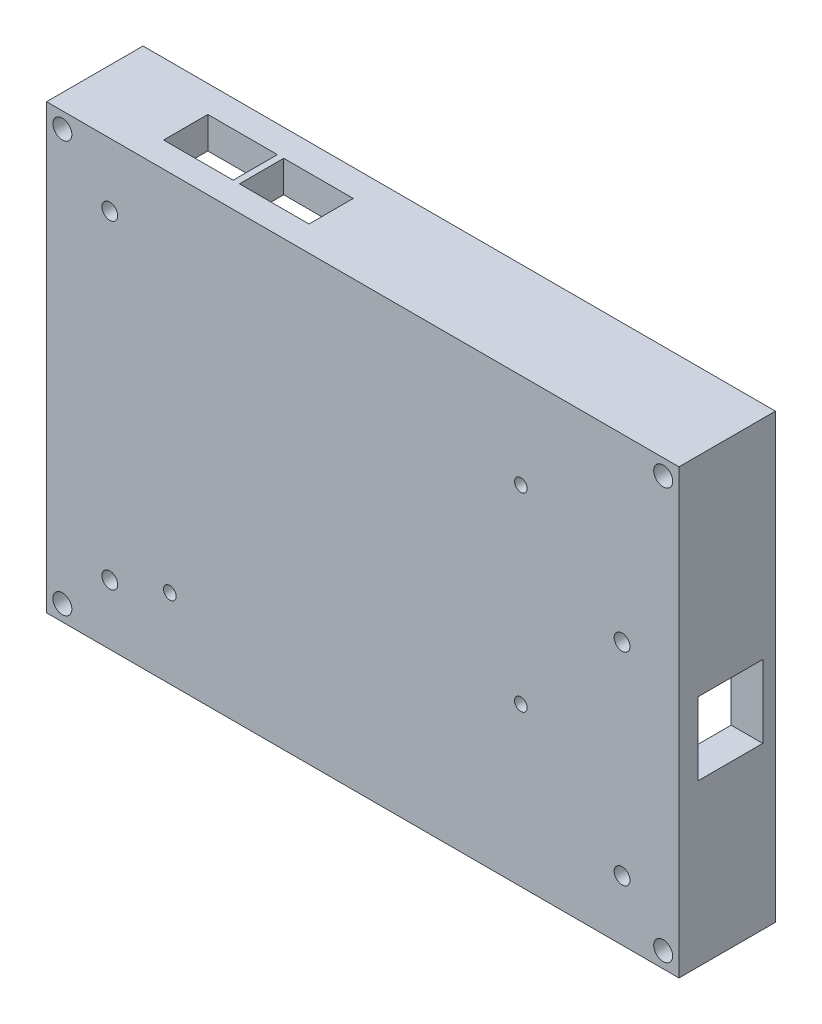
SolidWorks part; units mm, degrees
ref_plane "Front Plane" through (0, 0, 0) normal (0, 0, 1) x (1, 0, 0)
ref_plane "Top Plane" through (0, 0, 0) normal (0, 1, 0) x (1, 0, 0)
ref_plane "Right Plane" through (0, 0, 0) normal (1, 0, 0) x (0, 0, -1)
sketch "Sketch1" plane through (0, 0, 0) normal (0, 0, 1) x (1, 0, 0)
  line L0 (19.5, 57.5) -> (70.5, 57.5)
  line L1 (5, 5) -> (95, 5)
  line L2 (5, 5) -> (5, 65)
  line L3 (5, 65) -> (95, 65)
  line L4 (95, 5) -> (95, 65)
  line L5 (70.5, 57.5) -> (70.5, 27.5)
  line L6 (70.5, 27.5) -> (52.5, 27.5)
  line L7 (52.5, 27.5) -> (52.5, 12.5)
  line L8 (50, 65) -> (50, 70) construction
  line L9 (0, 0) -> (100, 0)
  line L10 (0, 0) -> (0, 70)
  line L11 (0, 70) -> (100, 70)
  line L12 (100, 0) -> (100, 70)
  line L13 (5, 35) -> (0, 35) construction
  line L14 (50, 5) -> (50, 0) construction
  line L15 (95, 35) -> (100, 35) construction
  line L16 (5, 65) -> (0, 70) construction
  line L17 (52.5, 12.5) -> (32.5, 12.5)
  line L18 (32.5, 12.5) -> (32.5, 32.5)
  line L19 (32.5, 32.5) -> (19.5, 32.5)
  line L20 (19.5, 32.5) -> (19.5, 57.5)
  line L21 (7.5, 35) -> (5, 35) construction
  line L22 (44.5, 52) -> (54.5, 52)
  line L23 (44.5, 52) -> (44.5, 46)
  line L24 (44.5, 46) -> (54.5, 46)
  line L25 (54.5, 52) -> (54.5, 46)
  line L26 (7.5, 62.5) -> (92.5, 62.5) construction
  line L27 (7.5, 62.5) -> (7.5, 7.5) construction
  line L28 (7.5, 7.5) -> (92.5, 7.5) construction
  line L29 (92.5, 62.5) -> (92.5, 7.5) construction
  line L30 (95, 35) -> (92.5, 35) construction
  line L31 (50, 5) -> (50, 7.5) construction
  line L32 (50, 65) -> (50, 62.5) construction
  line L33 (5, 12) -> (13, 12)
  line L34 (13, 12) -> (13, 5)
  line L35 (95, 13) -> (87.5, 13)
  line L36 (87.5, 13) -> (87.5, 5)
  line L37 (100, 70) -> (95, 65) construction
  line L38 (100, 0) -> (95, 5) construction
  line L39 (5, 5) -> (0, 0) construction
  line L40 (87.5, 45) -> (95, 45)
  line L41 (87.5, 45) -> (87.5, 38)
  line L42 (87.5, 38) -> (95, 38)
  line L43 (5, 56.5) -> (13.5, 56.5)
  line L44 (13.5, 56.5) -> (13.5, 65)
  line L45 (32.5, 12.5) -> (19.5, 12.5) construction
  line L46 (75, 65) -> (75, 55) construction
  line L47 (75, 55) -> (95, 55) construction
  line L48 (95, 25) -> (75, 25) construction
  line L49 (75, 25) -> (75, 5) construction
  circle A0 centre (2.5, 2.5) radius 1.5
  circle A1 centre (2.5, 67.5) radius 1.5
  circle A2 centre (97.5, 67.5) radius 1.5
  circle A3 centre (97.5, 2.5) radius 1.5
  circle A4 centre (10, 9.5) radius 0.625
  circle A5 centre (10, 60) radius 0.625
  circle A6 centre (91, 41.5) radius 0.625
  circle A7 centre (91, 9.5) radius 0.625
  circle A8 centre (10, 9.5) radius 1.25
  circle A9 centre (10, 60) radius 1.25
  circle A10 centre (91, 41.5) radius 1.25
  circle A11 centre (91, 9.5) radius 1.25
  circle A12 centre (10, 9.5) radius 1.75
  circle A13 centre (91, 9.5) radius 1.75
  circle A14 centre (91, 41.5) radius 1.75
  circle A15 centre (10, 60) radius 1.75
  circle A16 centre (19.5, 12.5) radius 1
  circle A17 centre (75, 55) radius 1
  circle A18 centre (75, 25) radius 1
  point P63 (10, 11.25)
  point P65 (11.75, 9.5)
  point P68 (91, 11.25)
  point P70 (89.25, 9.5)
  point P74 (89.25, 41.5)
  point P76 (91, 39.75)
  point P77 (91, 43.25)
  point P81 (11.75, 60)
  point P82 (10, 58.25)
  dimension "D16" = 3
  dimension "D5" = 1.25
  dimension "D14" = 2.5
  dimension "D30" = 3.5
  dimension "D31" = 0.75
  dimension "D40" = 2
  dimension "D2" = 70
  dimension "D3" = 12
  dimension "D4" = 5
  dimension "D6" = 37
  dimension "D7" = 5
  dimension "D8" = 18
  dimension "D9" = 6
  dimension "D10" = 10
  dimension "D11" = 100
  dimension "D12" = 85
  dimension "D13" = 55
  dimension "D15" = 22
  dimension "D17" = 40
  dimension "D18" = 20
  dimension "D19" = 25
  dimension "D20" = 25
  dimension "D21" = 5
  dimension "D22" = 2.5
  dimension "D23" = 2.5
  dimension "D24" = 1.5
  dimension "D25" = 21
  dimension "D26" = 1.5
  dimension "D27" = 2
  dimension "D28" = 2.5
  dimension "D29" = 2
  dimension "D32" = 1.25
  dimension "D33" = 1.75
  dimension "D34" = 1.75
  dimension "D35" = 1.75
  dimension "D36" = 1.75
  dimension "D37" = 1.75
  dimension "D38" = 1.75
  dimension "D39" = 1.75
  dimension "D41" = 20
  dimension "D42" = 10
  dimension "D44" = 20
extrude "Boss-Extrude6" add sketch "Sketch1" along normal blind 2 contours L9 L12 L11 L10 A3 A2 A1 A0 L4 L1 L2 L3 | L43 L44 L3 L2 A15 | A15 A9 | L34 L33 L2 L1 A12 | A12 A8 | L35 L36 L1 L4 A13 | A13 A11 | L41 L42 L4 L40 A14 | A14 A10 | L44 L43 L2 L33 L34 L1 L36 L35 L4 L42 L41 L40 L3 L19 L20 L0 L5 L6 L7 L17 L18 | L20 L19 L18 L17 L7 L6 L5 L0 L22 L25 L24 L23 | L25 L22 L23 L24 region at (45.1261, 38.7889, 0) region at (5.1063, 8.5, 0) region at (14.0817, 8.5, 0) region at (87.6097, 9, 0) region at (5.1202, 60.75, 0) region at (91.25, 38.1026, 0) region at (1.2207, 35, 0) region at (49.5, 49, 0) region at (8.2995, 9.5, 0) region at (89.2995, 9.5, 0) region at (89.2995, 41.5, 0) region at (8.2995, 60, 0)
extrude "Boss-Extrude7" add sketch "Sketch1<16>" against normal blind 7 contours A14 A10 | A10 A6 | A13 A11 | A11 A7 | A12 A8 | A8 A4 | A15 A9 | A9 A5 | L43 L44 L3 L2 A15 | L41 L42 L4 L40 A14 | L35 L36 L1 L4 A13 | L34 L33 L2 L1 A12 | L9 L12 L11 L10 A3 A2 A1 A0 L4 L1 L2 L3 region at (5.1063, 8.5, 0) region at (87.6097, 9, 0) region at (5.1202, 60.75, 0) region at (91.25, 38.1026, 0) region at (1.2207, 35, 0) region at (8.7854, 9.5, 0) region at (8.7854, 60, 0) region at (89.7854, 41.5, 0) region at (89.7854, 9.5, 0) region at (8.2995, 9.5, 0) region at (89.2995, 9.5, 0) region at (89.2995, 41.5, 0) region at (8.2995, 60, 0)
sketch "Sketch1<16>" plane through (0, 0, 0) normal (0, 0, 1) x (1, 0, 0) same geometry as "Sketch1"
extrude "Boss-Extrude8" add sketch "Sketch1<18>" against normal blind 5.5 contours L20 L19 L18 L17 L7 L6 L5 L0 L22 L25 L24 L23 region at (45.1261, 38.7889, 0)
sketch "Sketch1<18>" plane through (0, 0, 0) normal (0, 0, 1) x (1, 0, 0) same geometry as "Sketch1"
extrude "Cut-Extrude2" cut sketch "Sketch1<19>" against normal blind 5.75 contours A9 A5 | A8 A4 | A11 A7 | A10 A6 region at (8.7854, 9.5, 0) region at (8.7854, 60, 0) region at (89.7854, 41.5, 0) region at (89.7854, 9.5, 0)
sketch "Sketch1<19>" plane through (0, 0, 0) normal (0, 0, 1) x (1, 0, 0) same geometry as "Sketch1"
extrude "Boss-Extrude9" add sketch "Sketch1<20>" against normal blind 13.25 contours L9 L12 L11 L10 A3 A2 A1 A0 L4 L1 L2 L3 region at (1.2207, 35, 0)
sketch "Sketch1<20>" plane through (0, 0, 0) normal (0, 0, 1) x (1, 0, 0) same geometry as "Sketch1"
sketch "Sketch4" plane through (100, 0, 0) normal (1, 0, 0) x (0, 0, -1)
  line L1 (-2, 0) -> (13.25, 0) construction
  line L2 (13.25, 0) -> (13.25, 70) construction
  line L3 (-2, 0) -> (-2, 70) construction
  line L12 (11.25, 25.5) -> (1, 25.5)
  line L13 (11.25, 25.5) -> (11.25, 37)
  line L14 (11.25, 37) -> (1, 37)
  line L15 (1, 25.5) -> (1, 37)
  dimension "D1" = 2
  dimension "D2" = 3
  dimension "D3" = 25.5
  dimension "D4" = 11.5
extrude "Cut-Extrude3" cut sketch "Sketch4" against normal up to surface (5 mm away) up to face at (95, 33.2, -5.45)
sketch "Sketch5" plane through (0, 0, 0) normal (-1, 0, 0) x (0, 0, 1)
  line L0 (2, 0) -> (-13.25, 0) construction
  line L1 (-7, 16.5) -> (-6, 16.5) construction
  line L2 (-7, 16.5) -> (-7, 19.5) construction
  line L3 (-7, 19.5) -> (-6, 19.5) construction
  line L4 (-6, 16.5) -> (-6, 19.5) construction
  line L5 (-8.375, 18) -> (-7, 18) construction
  line L6 (-13.25, 0) -> (-13.25, 70) construction
  line L10 (-4.625, 22.25) -> (-8.375, 22.25)
  line L11 (-4.625, 22.25) -> (-4.625, 13.75)
  line L12 (-4.625, 13.75) -> (-8.375, 13.75)
  line L13 (-4.625, 18) -> (-6, 18) construction
  line L14 (-8.375, 22.25) -> (-8.375, 13.75)
  dimension "D1" = 16.5
  dimension "D2" = 6.25
  dimension "D3" = 1
  dimension "D4" = 3
  dimension "D5" = 8.5
  dimension "D6" = 3.75
extrude "Cut-Extrude4" cut sketch "Sketch5" against normal up to surface (5 mm away) up to face at (5, 34.625, -6.8125)
sketch "Sketch6" plane through (0, 70, 0) normal (0, 1, 0) x (1, 0, 0)
  line L0 (0, 6) -> (18.5, 6) construction
  line L1 (0, -2) -> (0, 13.25) construction
  line L2 (18.5, 6) -> (18.5, 13.25) construction
  line L3 (0, 13.25) -> (100, 13.25) construction
  line L4 (20, 9) -> (20, 6) construction
  line L5 (18.5, 6) -> (21.5, 6) construction
  line L6 (18.5, 6) -> (18.5, 5) construction
  line L7 (18.5, 5) -> (21.5, 5) construction
  line L8 (21.5, 6) -> (21.5, 5) construction
  line L9 (14.5, 2) -> (25.5, 2)
  line L10 (14.5, 2) -> (14.5, 9)
  line L11 (14.5, 9) -> (25.5, 9)
  line L12 (25.5, 2) -> (25.5, 9)
  line L13 (20, 2) -> (20, 5) construction
  line L14 (30.5, 6) -> (30.5, 13.25) construction
  line L15 (32, 9) -> (32, 6) construction
  line L16 (30.5, 6) -> (33.5, 6) construction
  line L17 (30.5, 6) -> (30.5, 5) construction
  line L18 (30.5, 5) -> (33.5, 5) construction
  line L19 (33.5, 6) -> (33.5, 5) construction
  line L20 (26.5, 2) -> (37.5, 2)
  line L21 (26.5, 2) -> (26.5, 9)
  line L22 (26.5, 9) -> (37.5, 9)
  line L23 (37.5, 2) -> (37.5, 9)
  line L24 (32, 2) -> (32, 5) construction
  dimension "D1" = 18.5
  dimension "D2" = 7.25
  dimension "D3" = 3
  dimension "D4" = 1
  dimension "D5" = 11
  dimension "D6" = 7
  dimension "D7" = 7.25
  dimension "D8" = 3
  dimension "D9" = 1
  dimension "D10" = 11
  dimension "D11" = 7
  dimension "D12" = 30.5
extrude "Cut-Extrude5" cut sketch "Sketch6" against normal up to surface (5 mm away) up to face at (37.8333, 65, -6.75)
